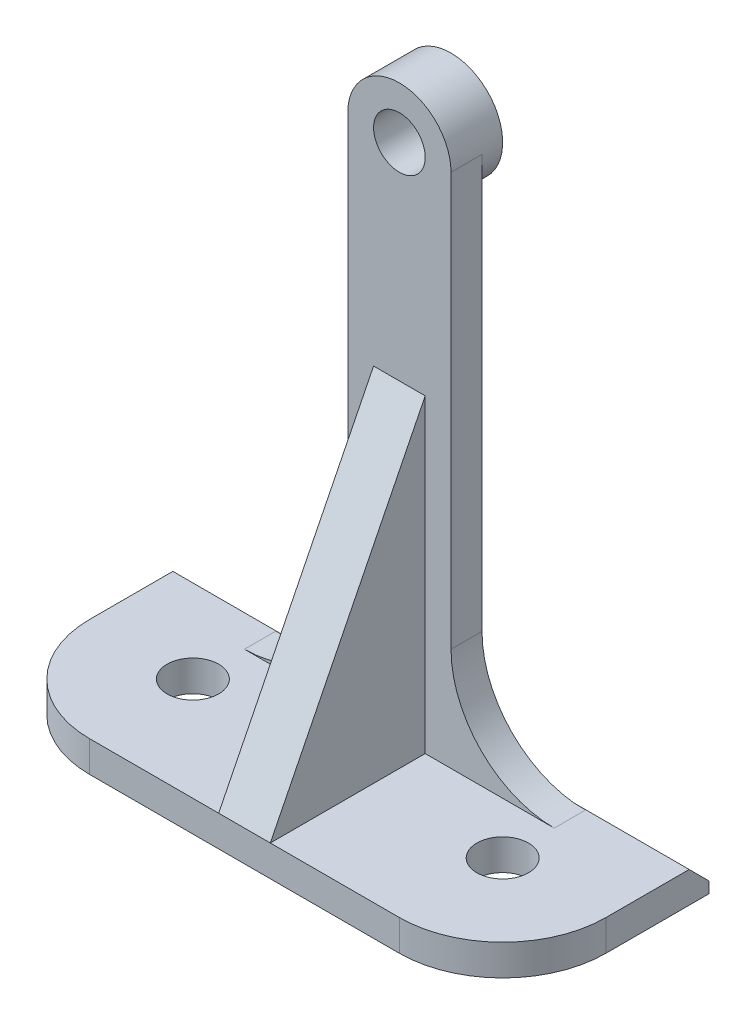
SolidWorks part; units mm, degrees
ref_plane "Front Plane" through (0, 0, 0) normal (0, 0, 1) x (1, 0, 0)
ref_plane "Top Plane" through (0, 0, 0) normal (0, 1, 0) x (1, 0, 0)
ref_plane "Right Plane" through (0, 0, 0) normal (1, 0, 0) x (0, 0, -1)
sketch "Sketch1" plane through (0, 0, 0) normal (0, 1, 0) x (1, 0, 0)
  line L1 (-63.5, 25.4) -> (63.5, 25.4)
  line L2 (-63.5, 25.4) -> (-63.5, 0)
  line L3 (-38.1, -25.4) -> (38.1, -25.4)
  line L4 (63.5, 25.4) -> (63.5, 0)
  line L5 (-63.5, 25.4) -> (63.5, -25.4) construction
  line L6 (-63.5, -25.4) -> (63.5, 25.4) construction
  arc A0 (38.1, -25.4) -> (63.5, 0) centre (38.1, 0) ccw
  arc A1 (-63.5, 0) -> (-38.1, -25.4) centre (-38.1, 0) ccw
  circle A3 centre (-38.1, 0) radius 6.35
  circle A4 centre (38.1, 0) radius 6.35
  point P0 (0, 0)
  point P12 (0, 0)
  dimension "D3" = 25.4
  dimension "D1" = 50.8
  dimension "D2" = 127
extrude "Boss-Extrude1" add sketch "Sketch1" along normal blind 7.62 contours L2 A1 L3 A0 L4 L1 | A3 | A4
sketch "Sketch4" plane through (0, 0, -25.4) normal (0, 0, -1) x (-1, 0, 0)
  line L0 (12.7, 134.62) -> (12.7, 7.62)
  line L1 (63.5, 7.62) -> (-63.5, 7.62) construction
  line L2 (-12.7, 134.62) -> (-12.7, 7.62)
  circle A0 centre (0, 134.62) radius 12.7
  circle A1 centre (0, 134.62) radius 6.35
  line M5 (63.5, 7.62) -> (-63.5, 7.62)
  dimension "D1" = 127
  dimension "D2" = 25.4
extrude "Boss-Extrude2" add sketch "Sketch4" against normal blind 7.62 from offset 5.08 contours A0 L2 L0 M5 | A0 A1 region at (0, 122.2792, -25.4) region at (0, 66.1671, -25.4) offset against normal yes
extrude "Boss-Extrude3" add sketch "Sketch4<3>" along normal blind 5.08 from offset 5.08 contours A0 A1 region at (0, 122.2792, -25.4) offset against normal yes
sketch "Sketch4<3>" plane through (0, 0, -25.4) normal (0, 0, -1) x (-1, 0, 0) same geometry as "Sketch4"
fillet "Fillet1" radius 25.4 2 edges at (-12.7, 7.62, -16.51) (12.7, 7.62, -16.51)
sketch "Sketch5" plane through (0, 0, 0) normal (1, 0, 0) x (0, 0, -1)
  line L0 (-25.4, 7.62) -> (12.7, 83.82)
  line L1 (12.7, 134.62) -> (12.7, 33.02) construction
rib "Rib1" sketch "Sketch5" sketch "Sketch5" thickness 12.7 extrusion direction parallel to sketch draft on no parameters "D1"=12.7
chamfer "Chamfer1" distance 4.92 angle 45 1 edges at (0, 7.62, -25.4)
